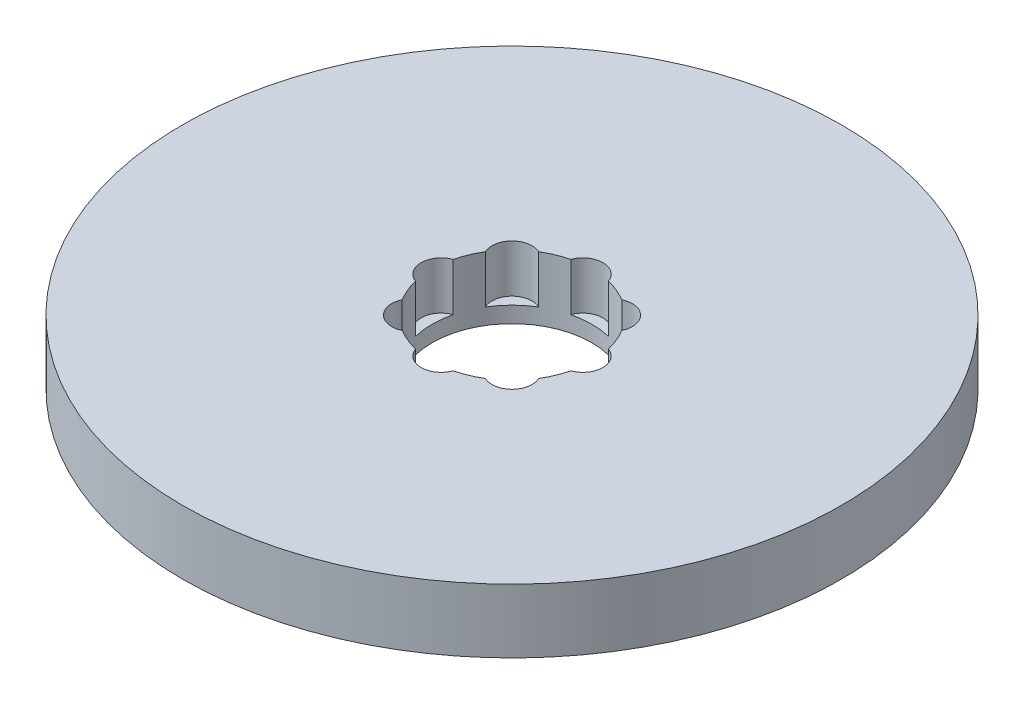
SolidWorks part; units mm, degrees
ref_plane "Front Plane" through (0, 0, 0) normal (0, 0, 1) x (1, 0, 0)
ref_plane "Top Plane" through (0, 0, 0) normal (0, 1, 0) x (1, 0, 0)
ref_plane "Right Plane" through (0, 0, 0) normal (1, 0, 0) x (0, 0, -1)
sketch "Sketch1" plane through (0, 0, 0) normal (0, 1, 0) x (1, 0, 0)
  circle A0 centre (0, 0) radius 82.5
  dimension "FLANGE_OD" = 165
extrude "Boss-Extrude1" add sketch "Sketch1" along normal blind 16
sketch "Sketch2" plane through (0, 0, 0) normal (0, 1, 0) x (1, 0, 0)
  circle A0 centre (0, 0) radius 20
  dimension "BORE_D" = 40
extrude "Cut-Extrude1" cut sketch "Sketch2" along normal through all
sketch "Sketch3" plane through (0, 16, 0) normal (0, 1, 0) x (1, 0, 0)
  circle A0 centre (0, 0) radius 17.7424 construction
  circle A1 centre (-17.7424, 0) radius 5.0091
  dimension "BOLT_D" = 10.0182
  dimension "BOLT_PCD" = 35.4848
extrude "Cut-Extrude2" cut sketch "Sketch3" against normal blind 11.9771
pattern_circular "CirPattern1" count 8 over 360 about axis through (0, 0, 0) along (0, 1, 0) of "Cut-Extrude2"
